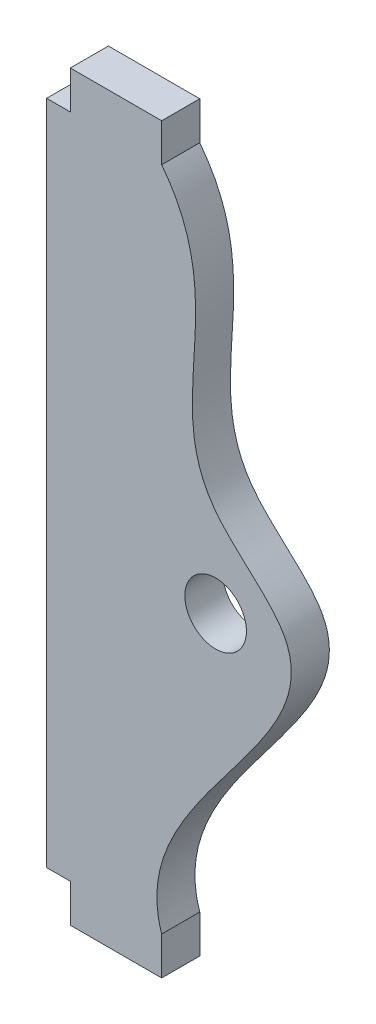
SolidWorks part; units mm, degrees
ref_plane "Alzado" through (0, 0, 0) normal (0, 0, 1) x (1, 0, 0)
ref_plane "Planta" through (0, 0, 0) normal (0, 1, 0) x (1, 0, 0)
ref_plane "Vista lateral" through (0, 0, 0) normal (1, 0, 0) x (0, 0, -1)
sketch "Croquis1" plane through (0, 0, 0) normal (0, 0, 1) x (1, 0, 0)
  line L0 (13.7481, -2) -> (-8.2747, -2) construction
  line L1 (-2.5, 15.5) -> (2.5, 15.5)
  line L2 (13.7481, -2) -> (13.7481, -19.5)
  line L3 (13.7481, -19.5) -> (2.5, -19.5)
  line L5 (13.7481, -19.5) -> (-3.5423, -19.5)
  line L6 (-3.5423, -19.5) -> (-3.5423, 15.5)
  line L7 (-2.3, 17.5) -> (2.5, 17.5)
  line L8 (-2.3, 17.5) -> (-2.3, 15.5)
  line L10 (2.5, 17.5) -> (2.5, 15.5)
  line L11 (-2.3, 17.5) -> (0, 15.5) construction
  line L12 (0, 15.5) -> (2.5, 17.5) construction
  line L13 (2.5, -21.5) -> (2.5, -19.5)
  line L14 (-2.3, -21.5) -> (2.5, -21.5)
  line L15 (-2.3, -21.5) -> (-2.3, -19.5)
  line L16 (-3.5423, 15.5) -> (-2.5, 15.5)
  circle A1 centre (5.3343, -3.4996) radius 1.6183
  spline S0 degree 3 poles (2.5, 15.5) (6.2813, 10.6134) (1.0207, 3.2256) (14.716, -5.5296) (0.4539, -13.3802) (2.5, -19.5) knots 0 0 0 0 0.382801 0.518825 1 1 1 1
  point P6 (0, 15.5)
  dimension "D1" = 35
  dimension "D2" = 4.8
  dimension "D3" = 2
extrude "Saliente-Extruir1" add sketch "Croquis1" along normal blind 2 contours S0 L1 L2 L3 | L10 L7 L8 L1 | L15 L14 L13 L3 region at (0.9665, -2.0804, 0) region at (0.1, 16.5, 0) region at (0.1, -20.5, 0)
